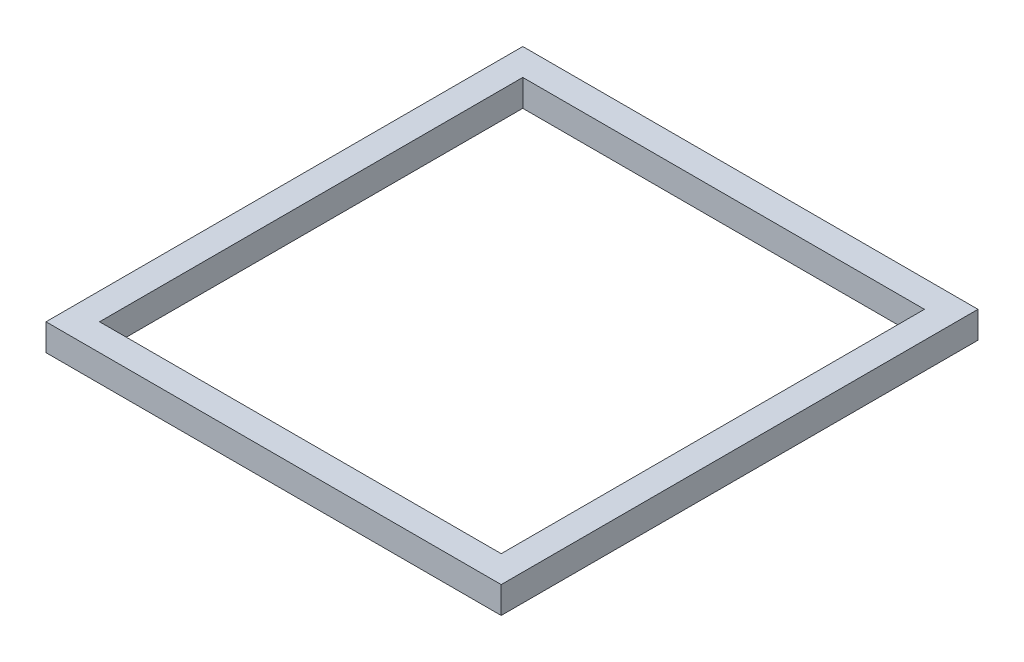
SolidWorks part; units mm, degrees
material "Silicon Rubber"
ref_plane "Front Plane" through (0, 0, 0) normal (0, 0, 1) x (1, 0, 0)
ref_plane "Top Plane" through (0, 0, 0) normal (0, 1, 0) x (1, 0, 0)
ref_plane "Right Plane" through (0, 0, 0) normal (1, 0, 0) x (0, 0, -1)
sketch "Sketch1" plane through (0, 0, 0) normal (0, 1, 0) x (1, 0, 0)
  line L1 (0, 0) -> (26.9875, 0)
  line L2 (0, 0) -> (0, 28.2675)
  line L3 (0, 28.2675) -> (26.9875, 28.2675)
  line L4 (26.9875, 0) -> (26.9875, 28.2675)
  line L5 (1.5875, 1.5875) -> (25.4, 1.5875)
  line L6 (1.5875, 1.5875) -> (1.5875, 26.68)
  line L7 (1.5875, 26.68) -> (25.4, 26.68)
  line L8 (25.4, 1.5875) -> (25.4, 26.68)
  dimension "D1" = 1.5875
  dimension "D2" = 1.5875
  dimension "D3" = 1.5875
  dimension "D4" = 1.5875
  dimension "D5" = 26.9875
  dimension "D6" = 28.2675
extrude "Boss-Extrude1" add sketch "Sketch1" along normal blind 1.5875
